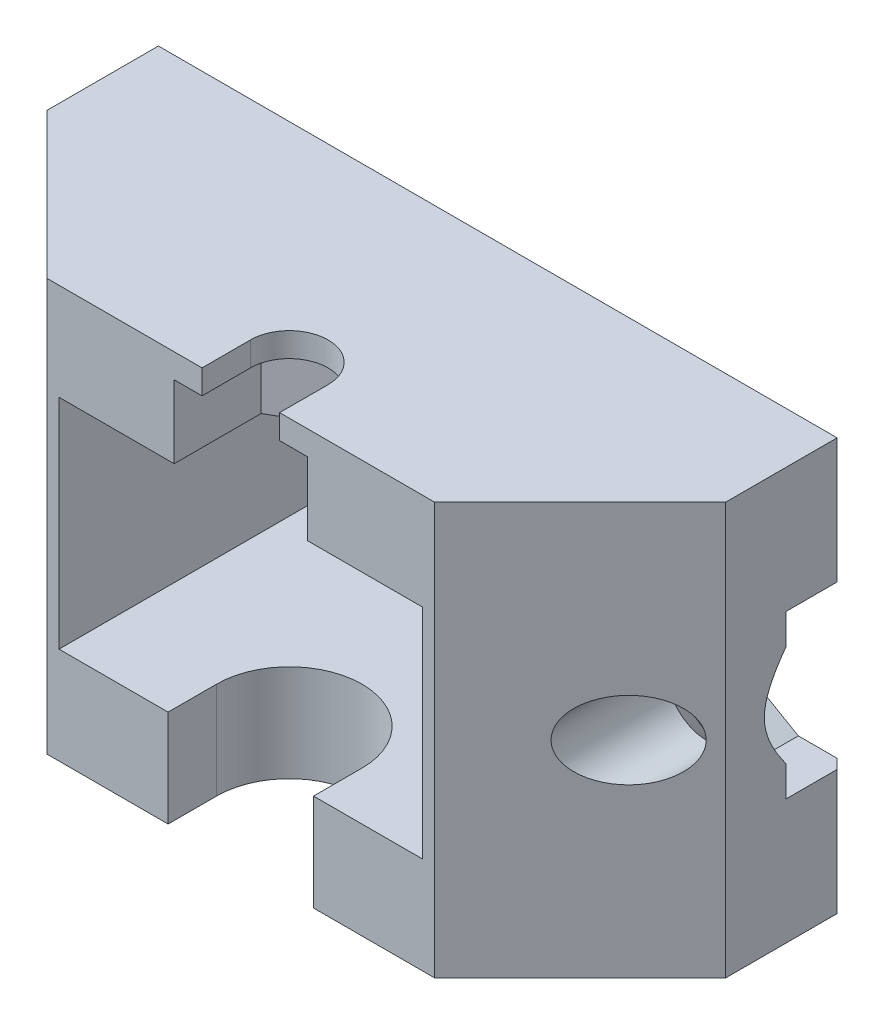
SolidWorks part; units mm, degrees
material "Custom Plastic"
ref_plane "Front Plane" through (0, 0, 0) normal (0, 0, 1) x (1, 0, 0)
ref_plane "Top Plane" through (0, 0, 0) normal (0, 1, 0) x (1, 0, 0)
ref_plane "Right Plane" through (0, 0, 0) normal (1, 0, 0) x (0, 0, -1)
sketch "Sketch1" plane through (0, 0, 0) normal (0, 0, 1) x (1, 0, 0)
  line L0 (14, 13) -> (14, 4) construction
  line L1 (0, 0) -> (28, 0)
  line L2 (0, 0) -> (0, 17)
  line L3 (0, 17) -> (28, 17)
  line L4 (28, 0) -> (28, 17)
  line L5 (6.5, 13) -> (21.5, 13)
  line L6 (6.5, 13) -> (6.5, 4)
  line L7 (6.5, 4) -> (21.5, 4)
  line L8 (21.5, 13) -> (21.5, 4)
  line L9 (14, 13) -> (14, 17) construction
  line L10 (6.5, 8.5) -> (21.5, 8.5) construction
  line L11 (6.5, 8.5) -> (0, 8.5) construction
  dimension "D1" = 17
  dimension "D2" = 28
  dimension "D3" = 15
  dimension "D4" = 9
extrude "Boss-Extrude1" add sketch "Sketch1" along normal blind 11
sketch "Sketch2" plane through (0, 0, 0) normal (0, -1, 0) x (1, 0, 0)
  line L0 (14, 11) -> (14, 9) construction
  line L1 (0, 11) -> (28, 11) construction
  line L2 (11, 9) -> (11, 11)
  line L3 (11, 11) -> (17, 11)
  line L4 (17, 11) -> (17, 9)
  line L5 (0, 0) -> (28, 0) construction
  arc A0 (11, 9) -> (17, 9) centre (14, 9) ccw
  dimension "D1" = 3
  dimension "D2" = 9
extrude "Cut-Extrude1" cut sketch "Sketch2" against normal up to surface (4 mm away) up to face at (14, 4, 5.5)
sketch "Sketch3" plane through (0, 13, 0) normal (0, -1, 0) x (1, 0, 0)
  line L0 (12.4, 9) -> (12.4, 11)
  line L1 (21.5, 11) -> (6.5, 11) construction
  line L2 (12.4, 11) -> (15.6, 11)
  line L3 (15.6, 11) -> (15.6, 9)
  arc A0 (12.4, 9) -> (15.6, 9) centre (14, 9) ccw
  arc A1 (11, 9) -> (17, 9) centre (14, 9) ccw construction
  dimension "D1" = 1.6
extrude "Cut-Extrude2" cut sketch "Sketch3" against normal through all
sketch "Sketch4" plane through (0, 13, 0) normal (0, -1, 0) x (1, 0, 0)
  line L0 (11.25, 11) -> (16.75, 11)
  line L1 (14, 5.8246) -> (16.75, 7.4123)
  line L2 (16.75, 7.4123) -> (16.75, 11)
  line L3 (18.0867, 9.816) -> (14, 12.1754) construction
  line L4 (14, 12.1754) -> (14.5574, 12.4972) construction
  line L5 (11.25, 11) -> (11.25, 7.4123)
  line L6 (11.25, 7.4123) -> (14, 5.8246)
  line L7 (12.4, 11) -> (6.5, 11) construction
  line L8 (21.5, 11) -> (15.6, 11) construction
  circle A0 centre (14, 9) radius 2.75 construction
  arc A1 (12.4, 9) -> (15.6, 9) centre (14, 9) ccw construction
  dimension "D1" = 5.5
extrude "Cut-Extrude3" cut sketch "Sketch4" against normal blind 3
chamfer "Chamfer4" distance 6 angle 45 2 edges at (28, 8.5, 11) (0, 8.5, 11)
sketch "Sketch6" plane through (0, 0, 11) normal (0, 0, 1) x (1, 0, 0)
  line L0 (28, 8.5) -> (26, 8.5) construction
  line L1 (28, 0) -> (28, 17) construction
  circle A0 centre (26, 8.5) radius 1.6
  dimension "D1" = 3.2
  dimension "D2" = 2
extrude "Cut-Extrude5" cut sketch "Sketch6" against normal through all
sketch "Sketch8" plane through (0, 0, 0) normal (0, 0, -1) x (-1, 0, 0)
  line L0 (-28, 5.1514) -> (-28, 11.8486)
  line L1 (-28.9, 10.1743) -> (-28.9, 6.8257) construction
  line L2 (-28.9, 6.8257) -> (-26, 5.1514) construction
  line L3 (-26, 5.1514) -> (-23.1, 6.8257)
  line L4 (-23.1, 6.8257) -> (-23.1, 10.1743)
  line L5 (-23.1, 10.1743) -> (-26, 11.8486)
  line L6 (-26, 11.8486) -> (-28.9, 10.1743) construction
  line L7 (-28, 0) -> (-28, 17) construction
  line L8 (-26, 11.8486) -> (-28, 11.8486)
  line L9 (-26, 5.1514) -> (-28, 5.1514)
  circle A0 centre (-26, 8.5) radius 2.9 construction
  dimension "D1" = 5.8
extrude "Cut-Extrude7" cut sketch "Sketch8" against normal blind 2.5
chamfer "Chamfer2" distance 1.3 angle 45 1 edges at (27.6, 8.5, 2.5)
chamfer "Chamfer3" distance 0.4 angle 45 8 edges at (14, 4, 0) (6.5, 8.5, 0) (14, 13, 0) (21.5, 8.5, 0) (28, 14.4243, 0) (28, 2.5757, 0) (14, 0, 0) (14, 17, 0)
ref_plane "Plane1" through (14, 0, 0) normal (1, 0, 0) x (0, 0, -1)
mirror "Mirror1" about plane through (14, 0, 0) normal (1, 0, 0) of "Chamfer2", "Cut-Extrude5", "Cut-Extrude7"
